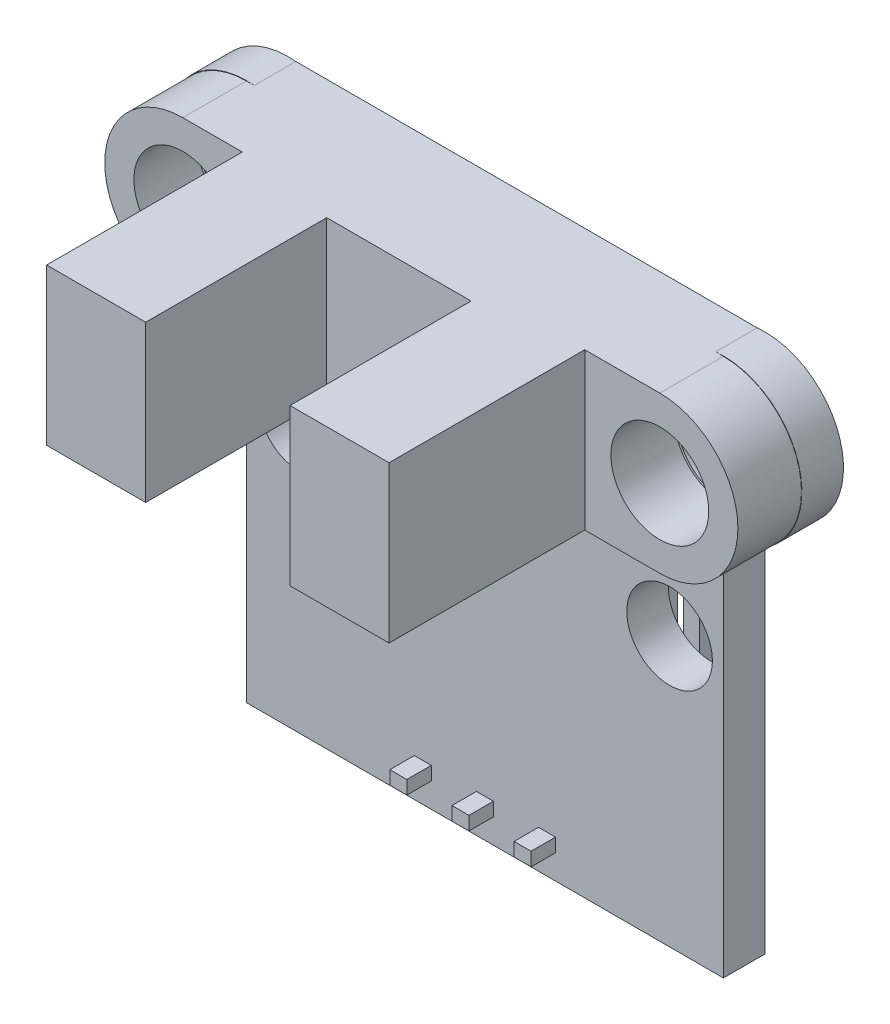
SolidWorks part; units mm, degrees
ref_plane "Ön Düzlem" through (0, 0, 0) normal (0, 0, 1) x (1, 0, 0)
ref_plane "Üst Düzlem" through (0, 0, 0) normal (0, 1, 0) x (1, 0, 0)
ref_plane "Sağ Düzlem" through (0, 0, 0) normal (1, 0, 0) x (0, 0, -1)
sketch "Çizim1" plane through (0, 0, 0) normal (0, 0, 1) x (1, 0, 0)
  line L0 (10.068, -11) -> (7.868, -11) construction
  line L1 (-9.432, -11) -> (10.068, -11)
  line L2 (-9.432, -11) -> (-9.432, 4.6)
  line L3 (-9.1139, 11) -> (9.75, 11)
  line L4 (10.068, -11) -> (10.068, 4.6)
  line L5 (7.868, -11) -> (7.868, 0) construction
  line L9 (0.318, 11) -> (0.318, -11) construction
  arc A0 (10.068, 4.6) -> (9.75, 11) centre (10.068, 7.8079) ccw
  circle A1 centre (10.068, 7.8079) radius 1.9006
  circle A2 centre (-9.432, 7.8079) radius 1.9006
  arc A3 (-9.432, 4.6) -> (-9.1139, 11) centre (-9.432, 7.8079) cw
  circle A4 centre (7.868, 0) radius 1.75
  circle A5 centre (-7.232, 0) radius 1.75
  point P0 (0, 0)
  dimension "D1" = 22
  dimension "D3" = 3.5
  dimension "D2" = 11
  dimension "D4" = 19.5
  dimension "D5" = 2.2
  dimension "D6" = 6.4
extrude "Yükseklik-Ekstrüzyon1" add sketch "Çizim1" along normal blind 1.7
sketch "Çizim2" plane through (0, 0, 1.7) normal (0, 0, 1) x (1, 0, 0)
  line L0 (-9.432, 11) -> (10.068, 11)
  line L1 (10.068, 4.6158) -> (-9.432, 4.6158)
  line L2 (9.75, 11) -> (-9.1139, 11) construction
  arc A0 (10.068, 4.6158) -> (10.068, 11) centre (10.068, 7.8079) ccw
  arc A1 (-9.432, 11) -> (-9.432, 4.6158) centre (-9.432, 7.8079) ccw
  circle A2 centre (-9.432, 7.8079) radius 2
  circle A3 centre (10.068, 7.8079) radius 2
extrude "Yükseklik-Ekstrüzyon2" add sketch "Çizim2" along normal blind 2.6
sketch "Çizim3" plane through (0, 0, 4.3) normal (0, 0, 1) x (1, 0, 0)
  line L0 (10.068, 11) -> (-9.432, 11) construction
  line L1 (0, 7.925) -> (0, 4.9813) construction
  line L2 (-9.432, 4.6158) -> (10.068, 4.6158) construction
  line L3 (2.95, 4.6158) -> (7.0001, 4.6158)
  line L4 (-7.0001, 11) -> (-2.95, 11)
  line L5 (-7.0001, 11) -> (-7.0001, 4.6158)
  line L6 (-7.0001, 4.6158) -> (-2.95, 4.6158)
  line L7 (7.0001, 11) -> (7.0001, 4.6158)
  line L11 (-2.95, 11) -> (-2.95, 4.6158)
  line L13 (2.95, 11) -> (2.95, 4.6158)
  line L18 (2.95, 11) -> (7.0001, 11)
  point P6 (0, 7.925)
  point P11 (0, 7.925)
  dimension "D1" = 5.9
extrude "Yükseklik-Ekstrüzyon3" add sketch "Çizim3" along normal blind 8
sketch "Çizim4" plane through (0, 0, 4.3) normal (0, 0, 1) x (1, 0, 0)
  line L4 (2.95, 11) -> (-2.95, 11)
  line L5 (-2.95, 11) -> (-2.95, 4.6158)
  line L6 (-2.95, 4.6158) -> (2.95, 4.6158)
  line L7 (2.95, 4.6158) -> (2.95, 11)
  line L8 (2.95, 11) -> (-2.95, 11)
  line L9 (-2.95, 11) -> (-2.95, 4.6158)
  line L10 (-2.95, 4.6158) -> (2.95, 4.6158)
  line L11 (2.95, 4.6158) -> (2.95, 11)
  dimension "D1" = 0
extrude "Yükseklik-Ekstrüzyon4" add sketch "Çizim4" along normal blind 0.6
sketch "Çizim5" plane through (0, 0, 0) normal (0, 0, -1) x (-1, 0, 0)
  line L0 (9.432, -11) -> (-10.068, -11) construction
  line L5 (-0.318, -11) -> (-0.318, -8.46) construction
  line L6 (0.702, -8.46) -> (0.952, -8.71)
  line L8 (-1.338, -8.46) -> (0.702, -8.46)
  line L9 (-1.588, -8.71) -> (-1.588, -10.75)
  line L10 (-1.338, -11) -> (0.702, -11)
  line L11 (0.952, -8.71) -> (0.952, -10.75)
  line L12 (-1.588, -8.46) -> (0.952, -11) construction
  line L13 (-1.588, -11) -> (0.952, -8.46) construction
  line L14 (0.702, -11) -> (0.952, -10.75)
  line L15 (-1.588, -10.75) -> (-1.338, -11)
  line L16 (-1.588, -8.71) -> (-1.338, -8.46)
  line L17 (-1.838, -11) -> (-3.878, -11)
  line L18 (-3.878, -11) -> (-4.128, -10.75)
  line L19 (-4.128, -8.71) -> (-4.128, -10.75)
  line L20 (-3.878, -8.46) -> (-4.128, -8.71)
  line L21 (-1.838, -8.46) -> (-3.878, -8.46)
  line L22 (-1.588, -10.75) -> (-1.838, -11)
  line L23 (-1.588, -8.71) -> (-1.838, -8.46)
  line L24 (3.242, -11) -> (1.202, -11)
  line L25 (1.202, -11) -> (0.952, -10.75)
  line L26 (1.202, -8.46) -> (0.952, -8.71)
  line L27 (3.242, -8.46) -> (1.202, -8.46)
  line L28 (3.492, -10.75) -> (3.242, -11)
  line L29 (3.492, -8.71) -> (3.242, -8.46)
  line L30 (3.492, -8.71) -> (3.492, -10.75)
  point P0 (-0.318, -11)
  point P3 (-0.318, -9.73)
  line M15 (-10.068, -11) -> (9.432, -11)
extrude "Yükseklik-Ekstrüzyon6" add sketch "Çizim5" along normal blind 2.54 contours L9 L23 L21 L20 L19 L18 L22 M15 | L16 L9 L15 L14 L11 L6 L8 M15 | L30 L29 L27 L26 L11 L25 L28 M15 region at (0.318, -9.73, 0) region at (-2.222, -9.73, 0) region at (2.858, -9.73, 0)
sketch "Çizim6" plane through (0, -11, 0) normal (0, -1, 0) x (1, 0, 0)
  line L1 (-9.432, 1.7) -> (10.068, 1.7)
  line L2 (-9.432, 1.7) -> (-9.432, 0)
  line L3 (-9.432, 0) -> (10.068, 0)
  line L4 (10.068, 1.7) -> (10.068, 0)
extrude "Yükseklik-Ekstrüzyon7" add sketch "Çizim6" along normal blind 0.01
sketch "Çizim7" plane through (2.95, 0, 0) normal (-1, 0, 0) x (0, 0, 1)
  line L0 (4.9, 7.8079) -> (11.65, 7.8079) construction
  line L1 (4.9, 4.6158) -> (4.9, 11) construction
  line L3 (4.9, 8.1829) -> (11.65, 8.1829)
  line L4 (4.9, 8.1829) -> (4.9, 7.4329)
  line L5 (4.9, 7.4329) -> (11.65, 7.4329)
  line L6 (11.65, 8.1829) -> (11.65, 7.4329)
  line L7 (4.9, 8.1829) -> (11.65, 7.4329) construction
  line L8 (4.9, 7.4329) -> (11.65, 8.1829) construction
  point P4 (8.275, 7.8079)
extrude "Kes-Ekstrüzyon1" cut sketch "Çizim7" against normal blind 0.1 and the other way blind 5.9
sketch "Çizim8" plane through (0, 0, -2.54) normal (0, 0, -1) x (-1, 0, 0)
  line L0 (-1.588, -8.71) -> (-1.588, -10.75) construction
  line L3 (0.952, -8.71) -> (0.952, -10.75) construction
  line L4 (0.827, -10.875) -> (-1.463, -8.585) construction
  line L5 (0.702, -11) -> (0.952, -10.75) construction
  line L6 (-1.588, -8.71) -> (-1.338, -8.46) construction
  line L7 (2.5544, -9.3975) -> (1.8895, -9.3975)
  line L8 (-0.6505, -10.0625) -> (0.0144, -10.0625)
  line L9 (-0.6505, -10.0625) -> (-0.6505, -9.3975)
  line L10 (-0.6505, -9.3975) -> (0.0144, -9.3975)
  line L11 (0.0144, -10.0625) -> (0.0144, -9.3975)
  line L12 (-0.6505, -10.0625) -> (0.0144, -9.3975) construction
  line L13 (-0.6505, -9.3975) -> (0.0144, -10.0625) construction
  line L14 (1.8895, -10.0625) -> (1.8895, -9.3975)
  line L15 (2.5544, -10.0625) -> (1.8895, -10.0625)
  line L16 (2.5544, -10.0625) -> (2.5544, -9.3975)
  line L17 (-2.5256, -9.3975) -> (-3.1905, -9.3975)
  line L18 (-3.1905, -10.0625) -> (-3.1905, -9.3975)
  line L19 (-2.5256, -10.0625) -> (-3.1905, -10.0625)
  line L20 (-2.5256, -10.0625) -> (-2.5256, -9.3975)
  point P14 (-0.318, -9.73)
ref_plane "Düzlem1" through (0, 0, 0) normal (1, 0, 0) x (0, 0, -1)
sketch "Çizim9" plane through (0, 0, 0) normal (1, 0, 0) x (0, 0, -1)
  line L0 (2.54, -9.73) -> (4.04, -9.73)
  line L1 (4.54, -9.23) -> (4.54, -3.305)
  arc A0 (4.04, -9.73) -> (4.54, -9.23) centre (4.04, -9.23) ccw
  dimension "D1" = 0.5
sweep "Süpür1" add profiles "Çizim8" path "Çizim9"
sketch "Çizim10" plane through (0, 0, -2.54) normal (0, 0, -1) x (-1, 0, 0)
  line L20 (-1.838, -11) -> (-1.588, -10.75)
  line L21 (-1.588, -10.75) -> (-1.338, -11)
  line L22 (-1.338, -11) -> (0.702, -11)
  line L23 (0.702, -11) -> (0.952, -10.75)
  line L24 (0.952, -10.75) -> (1.202, -11)
  line L25 (1.202, -11) -> (3.242, -11)
  line L26 (3.242, -11) -> (3.492, -10.75)
  line L27 (3.492, -10.75) -> (3.492, -8.71)
  line L28 (3.492, -8.71) -> (3.242, -8.46)
  line L29 (3.242, -8.46) -> (1.202, -8.46)
  line L30 (1.202, -8.46) -> (0.952, -8.71)
  line L31 (0.952, -8.71) -> (0.702, -8.46)
  line L32 (0.702, -8.46) -> (-1.338, -8.46)
  line L33 (-1.338, -8.46) -> (-1.588, -8.71)
  line L34 (-1.588, -8.71) -> (-1.838, -8.46)
  line L35 (-1.838, -8.46) -> (-3.878, -8.46)
  line L36 (-3.878, -8.46) -> (-4.128, -8.71)
  line L37 (-4.128, -8.71) -> (-4.128, -10.75)
  line L38 (-4.128, -10.75) -> (-3.878, -11)
  line L39 (-3.878, -11) -> (-1.838, -11)
  line L40 (-1.838, -11) -> (-1.588, -10.75)
  line L41 (-1.588, -10.75) -> (-1.338, -11)
  line L42 (-1.338, -11) -> (0.702, -11)
  line L43 (0.702, -11) -> (0.952, -10.75)
  line L44 (0.952, -10.75) -> (1.202, -11)
  line L45 (1.202, -11) -> (3.242, -11)
  line L46 (3.242, -11) -> (3.492, -10.75)
  line L47 (3.492, -10.75) -> (3.492, -8.71)
  line L48 (3.492, -8.71) -> (3.242, -8.46)
  line L49 (3.242, -8.46) -> (1.202, -8.46)
  line L50 (1.202, -8.46) -> (0.952, -8.71)
  line L51 (0.952, -8.71) -> (0.702, -8.46)
  line L52 (0.702, -8.46) -> (-1.338, -8.46)
  line L53 (-1.338, -8.46) -> (-1.588, -8.71)
  line L54 (-1.588, -8.71) -> (-1.838, -8.46)
  line L55 (-1.838, -8.46) -> (-3.878, -8.46)
  line L56 (-3.878, -8.46) -> (-4.128, -8.71)
  line L57 (-4.128, -8.71) -> (-4.128, -10.75)
  line L58 (-4.128, -10.75) -> (-3.878, -11)
  line L59 (-3.878, -11) -> (-1.838, -11)
  dimension "D1" = 0
sketch "Çizim11" plane through (0, 0, 1.7) normal (0, 0, 1) x (1, 0, 0)
  line L0 (-0.952, -8.71) -> (-0.952, -10.75) construction
  line L1 (0.318, -8.46) -> (0.318, -11) construction
  line L2 (-0.702, -8.46) -> (1.338, -8.46) construction
  line L3 (1.338, -11) -> (-0.702, -11) construction
  line L4 (1.588, -8.71) -> (1.588, -10.75) construction
  line L5 (-1.8754, -10.0071) -> (-2.5686, -10.0071)
  line L6 (-0.0286, -9.4529) -> (0.6646, -9.4529)
  line L7 (-0.0286, -9.4529) -> (-0.0286, -10.0071)
  line L8 (-0.0286, -10.0071) -> (0.6646, -10.0071)
  line L9 (0.6646, -9.4529) -> (0.6646, -10.0071)
  line L10 (-0.0286, -9.4529) -> (0.6646, -10.0071) construction
  line L11 (-0.0286, -10.0071) -> (0.6646, -9.4529) construction
  line L12 (-2.5686, -9.4529) -> (-2.5686, -10.0071)
  line L13 (-1.8754, -9.4529) -> (-2.5686, -9.4529)
  line L14 (-1.8754, -9.4529) -> (-1.8754, -10.0071)
  line L15 (3.2046, -10.0071) -> (2.5114, -10.0071)
  line L16 (2.5114, -9.4529) -> (2.5114, -10.0071)
  line L17 (3.2046, -9.4529) -> (2.5114, -9.4529)
  line L18 (3.2046, -9.4529) -> (3.2046, -10.0071)
  point P14 (0.318, -9.73)
extrude "Yükseklik-Ekstrüzyon8" add sketch "Çizim11" along normal blind 1
sketch "Çizim12" plane through (0, 0, 0) normal (0, 0, -1) x (-1, 0, 0)
  line L0 (-10.068, 0) -> (-4.9982, 0) construction
  line L1 (-10.068, -11.01) -> (-10.068, 4.6) construction
  line L2 (-4.9982, 0) -> (-4.9982, 2.3312)
  line L3 (-4.9982, 2.3312) -> (-1.2034, 2.3312)
  line L4 (-1.2034, 2.3312) -> (-1.2034, -3.046)
  line L5 (-1.2034, -3.046) -> (-4.9982, -3.046)
  line L6 (-4.9982, -3.046) -> (-4.9982, 0)
extrude "Yükseklik-Ekstrüzyon9" add sketch "Çizim12" along normal blind 1.5
